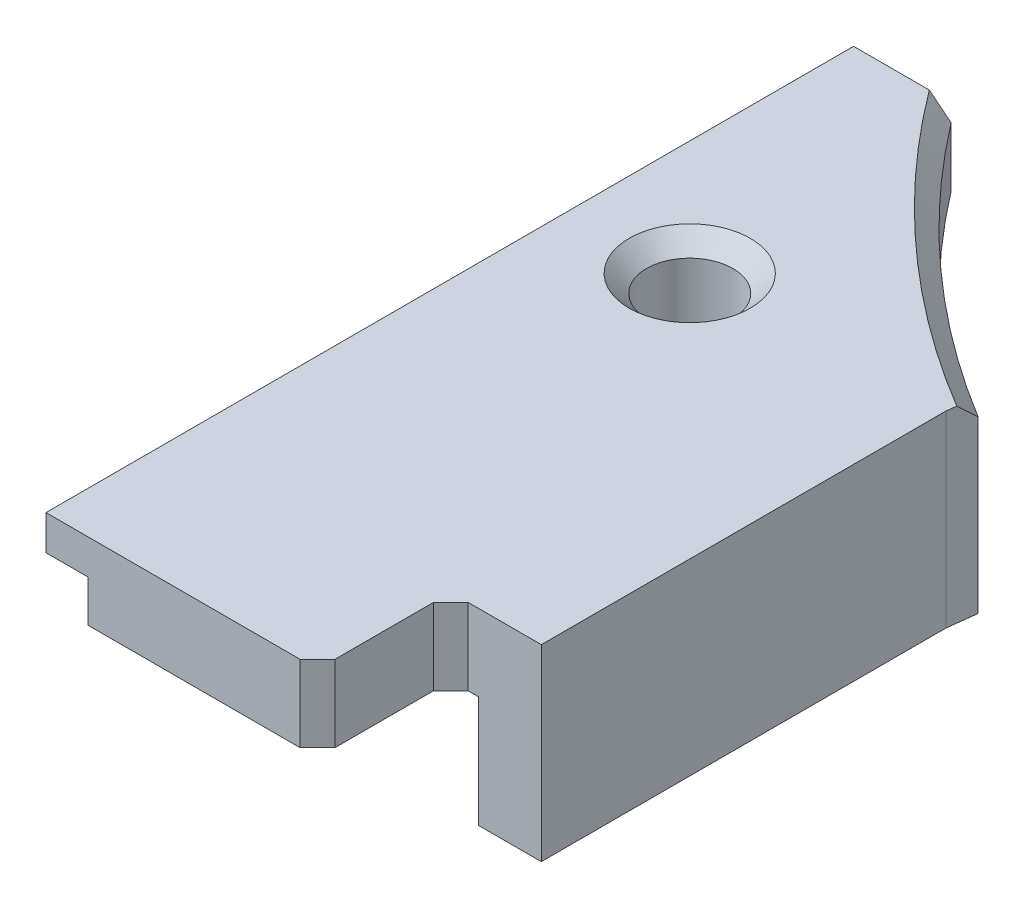
SolidWorks part; units mm, degrees
ref_plane "前视基准面" through (0, 0, 0) normal (0, 0, 1) x (1, 0, 0)
ref_plane "上视基准面" through (0, 0, 0) normal (0, 1, 0) x (1, 0, 0)
ref_plane "右视基准面" through (0, 0, 0) normal (1, 0, 0) x (0, 0, -1)
sketch "底座-前" plane through (0, 0, 0) normal (0, 1, 0) x (1, 0, 0)
  line L2 (-24.7152, 2.0807) -> (-24.5, 0.3125) construction
  line L6 (-22.5, -14.2499) -> (-22.5, -7.2636) construction
  line L7 (26.5, -14.2499) -> (22.5, -14.2499)
  line L8 (-22.5, -7.2636) -> (-24.5, -7.2636) construction
  line L9 (-24.5, -7.2636) -> (-24.5, 0.3125) construction
  line L10 (-24.5, 0.3125) -> (-25.1116, 5.3379) construction
  line L11 (22.5, -14.2499) -> (22.5, -7.2636)
  line L12 (-26.5, 1.2398) -> (-26.5, -14.2499) construction
  line L13 (-26.5, -14.2499) -> (-22.5, -14.2499) construction
  line L14 (22.5, -7.2636) -> (24.5, -7.2636)
  line L15 (26.5, 1.2398) -> (26.5, -14.2499)
  line L16 (-4.1009, 11.812) -> (-4.1009, 8.358) construction
  line L17 (-4.1009, 8.358) -> (4.1009, 8.358) construction
  line L18 (4.1009, 8.358) -> (4.1009, 11.8106) construction
  line L19 (-16.253, 10) -> (-4.1009, 10) construction
  line L20 (-4.1009, 10) -> (-4.1009, 8.358) construction
  line L21 (4.1009, 8.358) -> (4.1009, 10) construction
  line L22 (0, 0.0001) -> (0, -23.6618) construction
  line L23 (24.5, -7.2636) -> (24.5, 0.3125)
  line L24 (4.1009, 10) -> (12.5, 10) construction
  line L25 (12.5, 10) -> (12.5, -14.2499)
  line L26 (12.5, -14.2499) -> (-26.5, -14.2499) construction
  line L27 (24.7152, 2.0807) -> (24.5, 0.3125)
  line L28 (12.5, 10) -> (16.253, 10)
  line L29 (12.5, -14.2499) -> (22.5, -14.2499)
  arc A1 (-26.5, 2.4898) -> (-24.8662, 3.3216) centre (-28.6129, 8.6608) ccw construction
  arc A2 (26.5, 1.2398) -> (24.7152, 2.0807) centre (28.3556, 7.493) cw
  arc A3 (-25.1116, 5.3379) -> (-57.77, 17.2644) centre (-45.4537, 0.3125) ccw construction
  arc A4 (-26.5, 1.2398) -> (-24.7152, 2.0807) centre (-28.3556, 7.493) ccw construction
  arc A5 (-17.503, 10) -> (-24.8662, 3.3216) centre (-44.5319, 32.4021) cw construction
  arc A6 (-16.253, 10) -> (-24.7152, 2.0807) centre (-44.1427, 31.321) cw construction
  circle A7 centre (0, 6.108) radius 1.55 construction
  circle A8 centre (-16.866, 0) radius 1.55 construction
  arc A9 (16.253, 10) -> (24.7152, 2.0807) centre (44.1427, 31.321) ccw
  circle A10 centre (16.866, 0) radius 1.55
  dimension "D1" = 1.25
  dimension "D2" = 1.25
  dimension "D3" = 1.25
  dimension "D4" = 16.866
  dimension "D5" = 12.5
  dimension "D6" = 9.9999
  dimension "D7" = 14.25
  dimension "D8" = 22.5
  dimension "D9" = 26.5
  dimension "D10" = 24.5
  dimension "D11" = 7.2637
extrude "底座-1" add sketch "底座-前" along normal blind 2.75 contours A9 L28 L25 L29 L11 L14 L23 L27 region at (17.7884, 0, 3.1011)
sketch "底座-后" plane through (0, 0, 0) normal (0, 1, 0) x (1, 0, 0)
  line L0 (12.5, -14.2499) -> (12.5, -18.9999)
  line L1 (12.5, -18.9999) -> (22.5, -18.9999)
  line L2 (22.5, -18.9999) -> (22.5, -14.2499)
  line L3 (22.5, -14.2499) -> (12.5, -14.2499)
  dimension "D1" = 4.75
extrude "底座-2" add sketch "底座-后" along normal up to surface (2.75 mm away) up to face at (19.9549, 2.75, 2.6232)
sketch "底座卡榫" plane through (0, 0, 0) normal (0, 1, 0) x (1, 0, 0)
  line L1 (24.7152, 2.0807) -> (24.5, 0.3125)
  line L5 (0, 0) -> (0, 20.0235) construction
  line L6 (24.7152, 2.0807) -> (24.5, 0.3125) construction
  line L11 (22.5, -18.9999) -> (22.5, -7.2636) construction
  line L17 (22.5, -7.2636) -> (24.5, -7.2636) construction
  line L21 (25.75, 0.3125) -> (26.2135, 4.1214) construction
  line L22 (25.75, 0.3125) -> (24.5, 0.3125) construction
  line L24 (25.8753, 1.3423) -> (25.75, 0.3125)
  line L25 (22.5, -14.2136) -> (23.5, -14.2136)
  line L26 (22.5, -7.2636) -> (22.5, -14.2136)
  line L27 (23.5, -7.2636) -> (22.5, -7.2636)
  line L28 (24.5, -7.2636) -> (24.5, -14.2136)
  line L29 (24.5, -7.2636) -> (24.5, 0.3125)
  line L30 (25.75, -14.2136) -> (25.75, 0.3125)
  line L31 (24.5, -14.2136) -> (25.75, -14.2136)
  line L32 (23.5, -14.2136) -> (24.5, -14.2136)
  line L33 (23.5, -7.2636) -> (23.5, -14.2136)
  line L34 (24.5, -7.2636) -> (23.5, -7.2636)
  line L35 (24.5, -7.2636) -> (24.5, 0.3125) construction
  arc A2 (24.7152, 2.0807) -> (25.8753, 1.3423) centre (44.1427, 31.321) ccw
  arc A3 (16.253, 10) -> (24.7152, 2.0807) centre (44.1427, 31.321) ccw construction
  point P15 (25.125, -14.2136)
  dimension "D1" = 1.25
  dimension "D2" = 6.95
  dimension "D3" = 1
extrude "底座卡榫补齐" add sketch "底座卡榫" along normal up to surface (2.75 mm away) contours A2 L1 L29 L28 L31 L30 L24 | L28 L34 L33 L32 | L33 L27 L26 L25 region at (25.1278, 0, 6.2521) region at (24, 0, 10.7386) region at (23, 0, 10.7386) up to face at (19.9549, 2.75, 3.8107)
extrude "底座卡榫-注意PCB突出部分" add sketch "底座卡榫<6>" against normal blind 4 contours L28 L34 L33 L32 | A2 L1 L29 L28 L31 L30 L24 region at (25.1278, 0, 6.2521) region at (24, 0, 10.7386)
sketch "底座卡榫<6>" plane through (0, 0, 0) normal (0, 1, 0) x (1, 0, 0) same geometry as "底座卡榫"
sketch "草图4" plane through (0, 0, 0) normal (0, 1, 0) x (1, 0, 0)
  line L0 (12.5, 10) -> (14.25, 10)
  line L1 (12.5, 10) -> (16.253, 10) construction
  line L2 (14.25, 10) -> (14.25, -18.9999)
  line L3 (12.5, -18.9999) -> (22.5, -18.9999) construction
  line L4 (14.25, -18.9999) -> (12.5, -18.9999)
  line L5 (12.5, -18.9999) -> (12.5, 10)
  dimension "D1" = 1.75
extrude "卡榫切除" cut sketch "草图4" along normal blind 1.5
sketch "草图5" plane through (0, 0, 0) normal (0, 1, 0) x (1, 0, 0)
  line L0 (12.5, 10) -> (12.75, 10)
  line L1 (12.5, 10) -> (16.253, 10) construction
  line L2 (12.75, 10) -> (12.75, -18.9999)
  line L3 (12.5, -18.9999) -> (22.5, -18.9999) construction
  line L4 (12.75, -18.9999) -> (12.5, -18.9999)
  line L5 (12.5, -18.9999) -> (12.5, 10)
  dimension "D1" = 0.25
extrude "配合切除-2" cut sketch "草图5" along normal through all
chamfer "倒角1" distance 0.625 angle 45 4 edges at (22.5, 1.375, 18.9999) (16.866, 2.75, 1.55) (20.6617, 2.75, -5.2238) (22.5, 1.375, 14.2136)
sketch "草图6" plane through (0, -4, 0) normal (0, -1, 0) x (1, 0, 0)
  line L0 (24.7152, -2.0807) -> (24.5, -0.3125)
  line L1 (24.5, -0.3125) -> (24.5, 7.2636)
  line L2 (24.5, 7.2636) -> (23.5, 7.2636)
  line L3 (23.5, 7.2636) -> (23.5, 7.5136)
  line L4 (23.5, 7.2636) -> (23.5, 14.2136) construction
  line L5 (23.5, 7.5136) -> (24.75, 7.5136)
  line L6 (24.75, 7.5136) -> (24.75, -0.3125)
  line L7 (24.75, -0.3125) -> (24.9466, -1.9283)
  arc A0 (25.8753, -1.3423) -> (24.7152, -2.0807) centre (44.1427, -31.321) ccw construction
  arc A1 (24.7152, -2.0807) -> (24.9466, -1.9283) centre (44.1427, -31.321) cw
  dimension "D1" = 0.25
  dimension "D2" = 0.25
  dimension "D3" = 0.2482
extrude "切除-拉伸4" cut sketch "草图6" against normal up to surface (4 mm away) from surface up to face at (16.866, 0, 1.55) starting at face at (24.7609, -4, 4.864)
